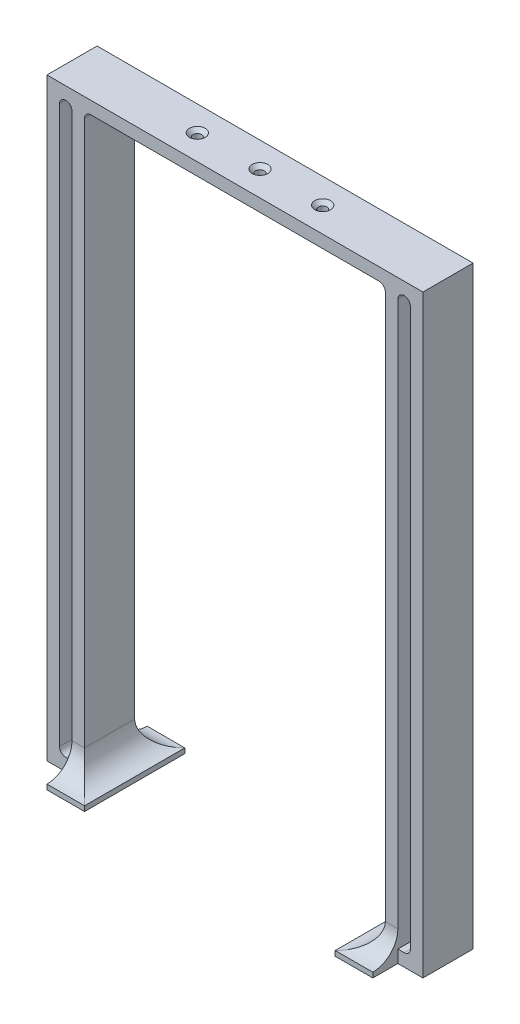
SolidWorks part; units mm, degrees
ref_plane "Front Plane" through (0, 0, 0) normal (0, 0, 1) x (1, 0, 0)
ref_plane "Top Plane" through (0, 0, 0) normal (0, 1, 0) x (1, 0, 0)
ref_plane "Right Plane" through (0, 0, 0) normal (1, 0, 0) x (0, 0, -1)
sketch "Sketch2" plane through (0, 0, 0) normal (0, 0, 1) x (1, 0, 0)
  line L0 (5, 12) -> (5, 232)
  line L1 (5, 232) -> (125, 232)
  line L2 (125, 232) -> (125, 12)
  line L3 (115, 0) -> (130, 0)
  line L4 (130, 0) -> (130, 237)
  line L5 (130, 237) -> (0, 237)
  line L6 (0, 237) -> (0, 0)
  line L9 (15, 0) -> (0, 0)
  line L13 (5, 12) -> (15, 12)
  line L14 (15, 0) -> (15, 12)
  line L17 (125, 12) -> (115, 12)
  line L18 (115, 0) -> (115, 12)
  line L19 (0, 237) -> (-5, 237)
  line L20 (0, 237) -> (0, 232)
  line L21 (0, 232) -> (-5, 232)
  line L22 (-5, 237) -> (-5, 232)
  line L23 (-5, 237) -> (-10, 237)
  line L24 (-5, 237) -> (-5, 0)
  line L25 (-5, 0) -> (-10, 0)
  line L26 (-10, 237) -> (-10, 0)
  line L27 (0, 0) -> (-5, 0)
  line L28 (0, 0) -> (0, 5)
  line L29 (0, 5) -> (-5, 5)
  line L30 (-5, 0) -> (-5, 5)
  line L31 (130, 237) -> (135, 237)
  line L32 (130, 237) -> (130, 232)
  line L33 (130, 232) -> (135, 232)
  line L34 (135, 237) -> (135, 232)
  line L35 (135, 237) -> (140, 237)
  line L36 (135, 237) -> (135, 0)
  line L37 (135, 0) -> (140, 0)
  line L38 (140, 237) -> (140, 0)
  line L39 (130, 0) -> (135, 0)
  line L40 (130, 0) -> (130, 5)
  line L41 (130, 5) -> (135, 5)
  line L42 (135, 0) -> (135, 5)
  dimension "D6" = 15
  dimension "D7" = 15
  dimension "D8" = 0
  dimension "D9" = 5
  dimension "D1" = 120
  dimension "D2" = 5
  dimension "D3" = 5
  dimension "D4" = 5
  dimension "D5" = 232
  dimension "D10" = 12
  dimension "D11" = 12
  dimension "D12" = 5
  dimension "D13" = 5
  dimension "D14" = 0
  dimension "D15" = 5
  dimension "D16" = 5
  dimension "D17" = 5
  dimension "D18" = 0
extrude "Boss-Extrude1" add sketch "Sketch2" along normal blind 20 contours L23 L26 L25 L24 L22 | L19 L22 L21 L6 | L6 L29 L24 L27 | L38 L35 L34 L36 L37 | L41 L4 L39 L36 | L34 L31 L4 L33 | L6 L9 L14 L13 L0 L1 L2 L17 L18 L3 L4 L5 region at (-2.5, 2.5, 0) region at (-7.5, 118.5, 0) region at (-2.5, 234.5, 0) region at (132.5, 2.5, 0) region at (137.5, 118.5, 0) region at (132.5, 234.5, 0)
sketch "Sketch3" plane through (0, 0, 0) normal (-1, 0, 0) x (0, 0, 1)
  line L1 (20, 0) -> (30, 0)
  line L2 (20, 0) -> (20, 12)
  line L4 (30, 0) -> (30, 2)
  line L5 (0, 0) -> (-10, 0)
  line L6 (0, 0) -> (0, 12)
  line L8 (-10, 0) -> (-10, 2)
  arc A0 (-10, 2) -> (0, 12) centre (-10, 12) ccw
  arc A1 (20, 12) -> (30, 2) centre (30, 12) ccw
  dimension "D1" = 12
  dimension "D2" = 12
  dimension "D3" = 10
  dimension "D4" = 10
  dimension "D5" = 2
  dimension "D6" = 2
extrude "Boss-Extrude2" add sketch "Sketch3" against normal up to surface (130 mm away) up to face at (130, 118.5, 10)
sketch "Sketch4" plane through (0, 0, 30) normal (0, 0, 1) x (1, 0, 0)
  line L0 (15, 2) -> (15, 0)
  line L1 (15, 0) -> (115, 0)
  line L3 (5, 12) -> (125, 12)
  line L5 (130, 2) -> (0, 2) construction
  line L6 (115, 2) -> (115, 0)
  arc A0 (5, 12) -> (15, 2) centre (15, 12) ccw
  arc A2 (115, 2) -> (125, 12) centre (115, 12) ccw
extrude "Cut-Extrude1" cut sketch "Sketch4" against normal blind 44 contours A0 L0 L1 L6 A2 L3
sketch "Sketch5" plane through (0, 0, 0) normal (0, -1, 0) x (1, 0, 0)
  line L0 (0, 30) -> (0, 20) construction
  line L1 (15, 30) -> (0, 30) construction
  line L2 (130, 30) -> (130, 20) construction
  line L3 (130, 30) -> (115, 30) construction
  point P0 (7.5, 10)
  point P1 (122.5, 10)
  dimension "D1" = 7.5
  dimension "D2" = 20
  dimension "D3" = 7.5
  dimension "D4" = 20
hole_wizard "Ø3.0mm Dowel Hole1" positions "Sketch5" profile "Sketch6" hole size "Ø3.0" standard "ANSI Metric"
sketch "Sketch6" plane through (7.5, 0, 10) normal (1, 0, 0) x (0, 0, -1)
  line L0 (0, 0) -> (0, 3.9013)
  line L1 (0, 3.9013) -> (1.5, 3)
  line L2 (1.5, 3) -> (1.5, 0)
  line L5 (1.5, 0) -> (0, 0)
  line L10 (0, 3.9013) -> (-1.5, 3) construction
  line L11 (0, -6.35) -> (0, 107.95) construction
  dimension "Hole Dia." = 3
  dimension "Hole Depth" = 3
  dimension "Drill Angle" = 118
sketch "Sketch7" plane through (0, 237, 0) normal (0, 1, 0) x (1, 0, 0)
  line L6 (15, 10) -> (15, -30) construction
  line L7 (115, 10) -> (115, -30) construction
  line L9 (140, 0) -> (-10, 0) construction
  line L10 (0, -20) -> (0, -30) construction
  point P0 (40, -10)
  point P1 (90, -10)
  point P9 (65, -10)
  dimension "D1" = 10
  dimension "D2" = 10
  dimension "D3" = 65
  dimension "D4" = 25
  dimension "D5" = 10
  dimension "D6" = 25
hole_wizard "CSK for M3 Flat Head Machine Screw1" positions "Sketch7" profile "Sketch9" countersink size "M3" standard "ANSI Metric" end condition up to next
sketch "Sketch9" plane through (40, 237, 10) normal (1, 0, 0) x (0, 0, 1)
  line L0 (0, 0) -> (0, 5)
  line L1 (0, 5) -> (1.7, 5)
  line L2 (1.7, 5) -> (1.7, 1.45)
  line L3 (1.7, 1.45) -> (3.15, 0)
  line L5 (3.15, 0) -> (0, 0)
  line L6 (-1.7, 1.45) -> (-3.15, 0) construction
  line L11 (0, -6.35) -> (0, 107.95) construction
  dimension "Thru Hole Dia." = 3.4
  dimension "Thru Hole Depth" = 5
  dimension "Near C'Sink Dia." = 6.3
  dimension "Near C'Sink Angle" = 90
fillet "Fillet1" radius 2.5 8 edges at (130, 232, 10) (135, 232, 10) (125, 232, 10) (0, 232, 10) (-5, 232, 10) (5, 232, 10) (-5, 5, 10) (135, 5, 10)
